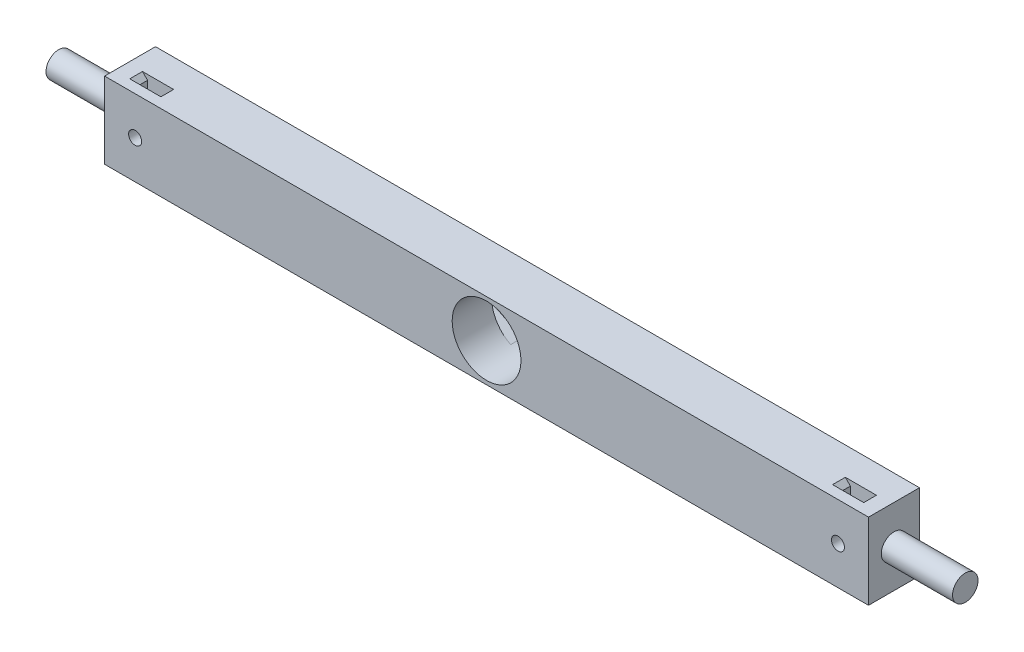
SolidWorks part; units mm, degrees
ref_plane "前视基准面" through (0, 0, 0) normal (0, 0, 1) x (1, 0, 0)
ref_plane "上视基准面" through (0, 0, 0) normal (0, 1, 0) x (1, 0, 0)
ref_plane "右视基准面" through (0, 0, 0) normal (1, 0, 0) x (0, 0, -1)
other "Configuration Table"
sketch "草图1" plane through (0, 0, 0) normal (0, 0, 1) x (1, 0, 0)
  line L0 (0, 0) -> (79.8665, 0) construction
  line L1 (0, 0) -> (0, 25.0088) construction
  line L2 (-150, 0) -> (-150, 30)
  line L3 (-150, 30) -> (150, 30)
  line L4 (150, 30) -> (150, 0)
  line L5 (150, 0) -> (-150, 0)
  point P7 (0, 30)
  dimension "D1" = 300
  dimension "D2" = 30
extrude "凸台-拉伸1" add sketch "草图1" along normal blind 20 contours L2 L3 L4 L5
sketch "草图2" plane through (-150, 0, 0) normal (-1, 0, 0) x (0, 0, 1)
  line L0 (0, 0) -> (0, 30) construction
  line L1 (0, 0) -> (0, 30) construction
  line L3 (0, 15) -> (20, 15) construction
  line L6 (0, 20) -> (0, 10)
  arc A0 (0, 10) -> (0, 20) centre (0, 15) ccw
  dimension "D1" = 5
sketch "草图3" plane through (0, 0, 0) normal (0, 0, -1) x (-1, 0, 0)
  line L0 (0, 0) -> (0, 129.1579) construction
  line L1 (-178, 15) -> (178, 15) construction
  line L2 (-6.0203, 27.0833) -> (-20.8412, 19.6991)
  line L3 (6.0203, 27.0833) -> (20.8412, 19.6991)
  line L4 (6.0203, 2.9167) -> (20.8412, 10.3009)
  line L5 (-6.0203, 2.9167) -> (-20.8412, 10.3009)
  circle A0 centre (0, 15) radius 4
  circle A1 centre (0, 15) radius 6
  circle A2 centre (0, 15) radius 13.25
  circle A3 centre (18.5, 15) radius 2.4
  circle A4 centre (0, 15) radius 13.5
  circle A5 centre (-18.5, 15) radius 2.4
  arc A6 (-20.8412, 19.6991) -> (-20.8412, 10.3009) centre (-18.5, 15) ccw
  arc A7 (20.8412, 19.6991) -> (20.8412, 10.3009) centre (18.5, 15) cw
  point P20 (-23.75, 15)
  dimension "D1" = 8
  dimension "D2" = 2
  dimension "D4" = 4.8
  dimension "D6" = 0.25
  dimension "D7" = 10.5
  dimension "D5" = 18.5
  dimension "D3" = 7.25
extrude "切除-拉伸1" cut sketch "草图3" against normal through all contours A0 region at (0, 15, 0)
extrude "切除-拉伸2" cut sketch "草图3<3>" against normal through all contours A1 A0 region at (5.8303, 15, 0)
sketch "草图3<3>" plane through (0, 0, 0) normal (0, 0, -1) x (-1, 0, 0) same geometry as "草图3"
extrude "切除-拉伸3" cut sketch "草图3<4>" against normal through all contours A2 A1 | A4 A2 region at (0, 28.4618, 0) region at (12.8752, 15, 0)
sketch "草图3<4>" plane through (0, 0, 0) normal (0, 0, -1) x (-1, 0, 0) same geometry as "草图3"
extrude "切除-拉伸4" cut sketch "草图3<5>" against normal blind 4.5 contours L2 A6 L5 A4 A5 | A7 L3 A4 L4 A3 region at (13.7997, 15, 0) region at (-13.2971, 23.1229, 0)
sketch "草图3<5>" plane through (0, 0, 0) normal (0, 0, -1) x (-1, 0, 0) same geometry as "草图3"
extrude "切除-拉伸5" cut sketch "草图3<6>" against normal blind 5 contours A5 | A3 region at (-18.5, 15, 0) region at (18.5, 15, 0)
sketch "草图3<6>" plane through (0, 0, 0) normal (0, 0, -1) x (-1, 0, 0) same geometry as "草图3"
sketch "草图4" plane through (-150, 0, 0) normal (-1, 0, 0) x (0, 0, 1)
  line L0 (20, 30) -> (0, 0) construction
  line L1 (0, -200000) -> (0, 200030) construction
  circle A0 centre (10, 15) radius 5
extrude "凸台-拉伸2" add sketch "草图4" along normal blind 28
ref_plane "基准面1" through (0, 0, 0) normal (-1, 0, 0) x (0, 0, 1)
mirror "镜向1" about plane through (0, 0, 0) normal (-1, 0, 0) of "凸台-拉伸2"
sketch "草图5" plane through (0, 0, 20) normal (0, 0, 1) x (1, 0, 0)
  line L0 (-138, 30) -> (-138, 0) construction
  line L1 (-150, 30) -> (150, 30) construction
  line L2 (-150, -200000) -> (-150, 200030) construction
  line L4 (150, 0) -> (-150, 0) construction
  circle A0 centre (-138, 15) radius 2.55
  dimension "D1" = 12
extrude "切除-拉伸6" cut sketch "草图5" against normal blind 4 contours A0
sketch "草图6" plane through (0, 0, 16) normal (0, 0, 1) x (1, 0, 0)
  line L0 (-138, 17.55) -> (-138, 12.45) construction
  line L1 (150, 0) -> (-150, 0) construction
  line L2 (-142.1085, 30) -> (-133.8915, 30)
  line L3 (-142.1085, 30) -> (-142.1085, 0)
  line L4 (-142.1085, 0) -> (-133.8915, 0)
  line L5 (-133.8915, 30) -> (-133.8915, 0)
  line L6 (-142.1085, 30) -> (-133.8915, 0) construction
  line L7 (-142.1085, 0) -> (-133.8915, 30) construction
  line L8 (-150, 30) -> (150, 30) construction
  circle A0 centre (-138, 15) radius 2.55 construction
  point P5 (-138, 15)
  point P12 (0, 0)
extrude "切除-拉伸7" cut sketch "草图6" against normal blind 5 contours L5 L4 L3 L2
chamfer "倒角1" distance 2 angle 45 4 edges at (-133.8915, 0, 13.5) (-142.1085, 0, 13.5) (-133.8915, 30, 13.5) (-142.1085, 30, 13.5)
mirror "镜向2" about plane through (0, 0, 0) normal (-1, 0, 0) of "倒角1", "切除-拉伸7", "切除-拉伸6"
